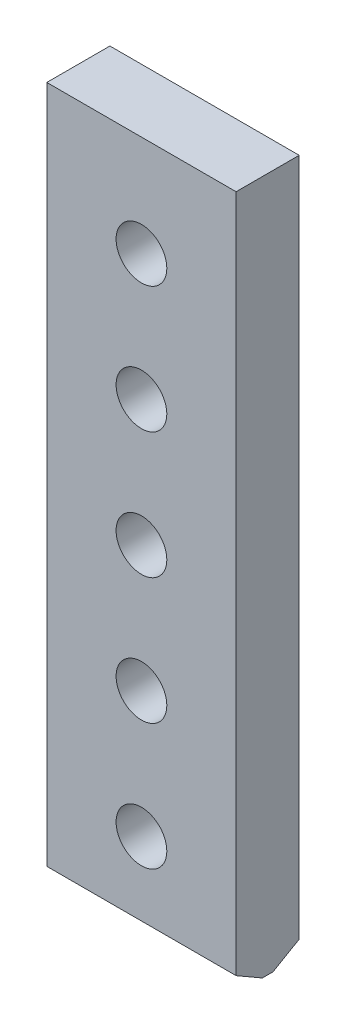
SolidWorks part; units mm, degrees
ref_plane "Спереди" through (0, 0, 0) normal (0, 0, 1) x (1, 0, 0)
ref_plane "Сверху" through (0, 0, 0) normal (0, 1, 0) x (1, 0, 0)
ref_plane "Справа" through (0, 0, 0) normal (1, 0, 0) x (0, 0, -1)
sketch "Эскиз1" plane through (0, 0, 0) normal (0, 0, 1) x (1, 0, 0)
  line L1 (0, 0) -> (75, 0)
  line L2 (0, 0) -> (0, 275)
  line L3 (0, 275) -> (75, 275)
  line L4 (75, 0) -> (75, 275)
  point P5 (37.5, 275)
  dimension "D1" = 275
  dimension "D2" = 75
extrude "Бобышка-Вытянуть1" add sketch "Эскиз1" along normal blind 25
sketch "Эскиз2" plane through (0, 0, 25) normal (0, 0, 1) x (1, 0, 0)
  line L0 (0, 0) -> (75, 0) construction
  line L1 (75, 0) -> (75, 275) construction
  circle A0 centre (37.5, 35) radius 10.05
  circle A1 centre (37.5, 85) radius 10.05
  circle A2 centre (37.5, 135) radius 10.05
  circle A3 centre (37.5, 185) radius 10.05
  circle A4 centre (37.5, 235) radius 10.05
  dimension "D1" = 5
  dimension "D2" = 35
  dimension "D3" = 37.5
  dimension "D4" = 20.1
extrude "Вырез-Вытянуть1" cut sketch "Эскиз2" against normal through all
chamfer "Фаска1" distance 6 angle 60 1 edges at (37.5, 0, 0) first distance on face at (47.55, 85, 0)
chamfer "Фаска2" distance 6 angle 60 1 edges at (37.5, 0, 25) first distance on face at (47.55, 85, 25)
